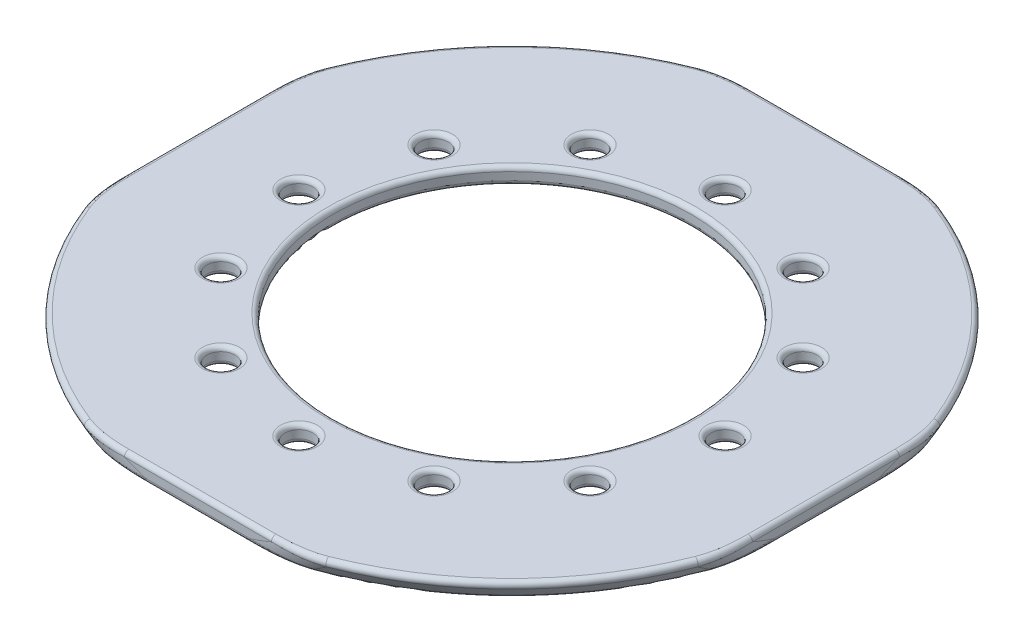
SolidWorks part; units mm, degrees
ref_plane "Front Plane" through (0, 0, 0) normal (0, 0, 1) x (1, 0, 0)
ref_plane "Top Plane" through (0, 0, 0) normal (0, 1, 0) x (1, 0, 0)
ref_plane "Right Plane" through (0, 0, 0) normal (1, 0, 0) x (0, 0, -1)
sketch "Main Revolve Sketch" plane through (0, 0, 0) normal (0, 0, 1) x (1, 0, 0)
  line L0 (0, 0) -> (0, 96.25) construction
  line L3 (-82.5, 13.75) -> (-82.5, 0) construction
  line L4 (-82.5, 0) -> (-82.5, -13.75) construction
  line L8 (0, 96.25) -> (96.25, 96.25) construction
  line L9 (0, -96.25) -> (96.25, -96.25) construction
  line L11 (0, 0) -> (0, -96.25) construction
  line L13 (0, 0) -> (0, -50) construction
  line L14 (0, -50) -> (-74.1093, -50)
  line L16 (0, -53.75) -> (-72.1543, -53.75)
  line L17 (0, -50) -> (0, -53.75)
  arc A0 (0, 96.25) -> (-82.5, 13.75) centre (0, 13.75) ccw construction
  arc A1 (-74.1093, -50) -> (-72.1543, -53.75) centre (0, -13.75) ccw
  dimension "D1" = 82.5
  dimension "D2" = 27.5
  dimension "D3" = 50
  dimension "D4" = 3.75
revolve "Main Revolve" add sketch "Main Revolve Sketch" angle 360 about L0
sketch "Sketch3" plane through (0, 0, 0) normal (0, 0, 1) x (1, 0, 0)
  circle A9 centre (0, 0) radius 125
  dimension "D1" = 250
extrude "Cut-Extrude2" cut sketch "Sketch3" against normal offset from surface (430 mm away) 70 from offset 500 contours A9 up to plane "Front Plane"
fillet "Fillet1" radius 10 2 edges at (-21.0013, -52.0279, 70) (21.0013, -52.0279, 70)
pattern_circular "CirPattern4" count 4 over 360 about axis through (0, -50, 0) along (0, -1, 0) of "Cut-Extrude2", "Fillet1"
sketch "Sketch5" plane through (0, 0, 0) normal (0, 1, 0) x (1, 0, 0)
  line L8 (0, 0) -> (0, -47.5) construction
  line L9 (-23.75, 41.1362) -> (0, 47.5) construction
  line L10 (47.5, 0) -> (0, 0) construction
  line L11 (0, 0) -> (41.1362, 23.75) construction
  line L12 (41.1362, 23.75) -> (23.75, 41.1362) construction
  line L13 (23.75, 41.1362) -> (0, 0) construction
  line L14 (0, 0) -> (0, 47.5) construction
  line L15 (0, 47.5) -> (23.75, 41.1362) construction
  line L16 (-23.75, 41.1362) -> (0, 0) construction
  line L17 (0, 0) -> (-41.1362, 23.75) construction
  line L18 (-41.1362, 23.75) -> (-47.5, 0) construction
  line L19 (-47.5, 0) -> (0, 0) construction
  line L20 (0, 0) -> (-41.1362, -23.75) construction
  line L21 (47.5, 0) -> (41.1362, 23.75) construction
  line L22 (-23.75, 41.1362) -> (-41.1362, 23.75) construction
  line L23 (-41.1362, -23.75) -> (-47.5, 0) construction
  line L24 (0, 0) -> (-23.75, -41.1362) construction
  line L25 (0, 0) -> (41.1362, -23.75) construction
  line L26 (-23.75, -41.1362) -> (-41.1362, -23.75) construction
  line L29 (41.1362, -23.75) -> (47.5, 0) construction
  line L30 (-23.75, -41.1362) -> (0, -47.5) construction
  line L31 (0, -47.5) -> (23.75, -41.1362) construction
  line L32 (23.75, -41.1362) -> (41.1362, -23.75) construction
  line L33 (0, 0) -> (23.75, -41.1362) construction
  circle A8 centre (0, 0) radius 40
  circle A9 centre (0, -47.5) radius 3.125
  circle A10 centre (47.5, 0) radius 3.125
  circle A11 centre (41.1362, 23.75) radius 3.125
  circle A12 centre (23.75, 41.1362) radius 3.125
  circle A13 centre (0, 47.5) radius 3.125
  circle A14 centre (-23.75, 41.1362) radius 3.125
  circle A15 centre (-41.1362, 23.75) radius 3.125
  circle A16 centre (-47.5, 0) radius 3.125
  circle A17 centre (-41.1362, -23.75) radius 3.125
  circle A18 centre (41.1362, -23.75) radius 3.125
  circle A19 centre (-23.75, -41.1362) radius 3.125
  circle A20 centre (23.75, -41.1362) radius 3.125
  dimension "D1" = 80
  dimension "D3" = 6.25
  dimension "D2" = 47.5
extrude "Cut-Extrude3" cut sketch "Sketch5" against normal through all
fillet "Fillet2" radius 1 58 edges at (-70, -53.75, 0) (-69.9464, -53.75, 11.8954) (-51.0208, -53.75, 51.0208) (0, -53.75, 70) (11.8954, -53.75, 69.9464) (51.0208, -53.75, 51.0208) (70, -53.75, 0) (69.9464, -53.75, -11.8954) (51.0208, -53.75, -51.0208) (0, -53.75, -70) (-11.8954, -53.75, -69.9464) (-51.0208, -53.75, -51.0208) (0, -53.75, 40) (23.75, -53.75, 44.2612) (-23.75, -53.75, 44.2612) (41.1362, -53.75, 26.875) (-41.1362, -53.75, 26.875) (0, -53.75, 50.625) (47.5, -53.75, 3.125) (41.1362, -53.75, -20.625) (23.75, -53.75, -38.0112) (0, -53.75, -44.375) (-23.75, -53.75, -38.0112) (-41.1362, -53.75, -20.625) (-47.5, -53.75, 3.125) (-52.4032, -50, -52.4032) (0, -50, -70) (22.0118, -50, -69.8522) (52.4032, -50, -52.4032) (70, -50, 0) (69.8522, -50, 22.0118) (52.4032, -50, 52.4032) (0, -50, 70) (-22.0118, -50, 69.8522) (-52.4032, -50, 52.4032) (-70, -50, 0) (-69.8522, -50, -22.0118) (0, -50, -40) (23.75, -50, 38.0112) (-23.75, -50, 38.0112) (41.1362, -50, 20.625) (-41.1362, -50, 20.625) (0, -50, 44.375) (47.5, -50, -3.125) (41.1362, -50, -26.875) (23.75, -50, -44.2612) (0, -50, -50.625) (-23.75, -50, -44.2612) (-41.1362, -50, -26.875) (-47.5, -50, -3.125)
